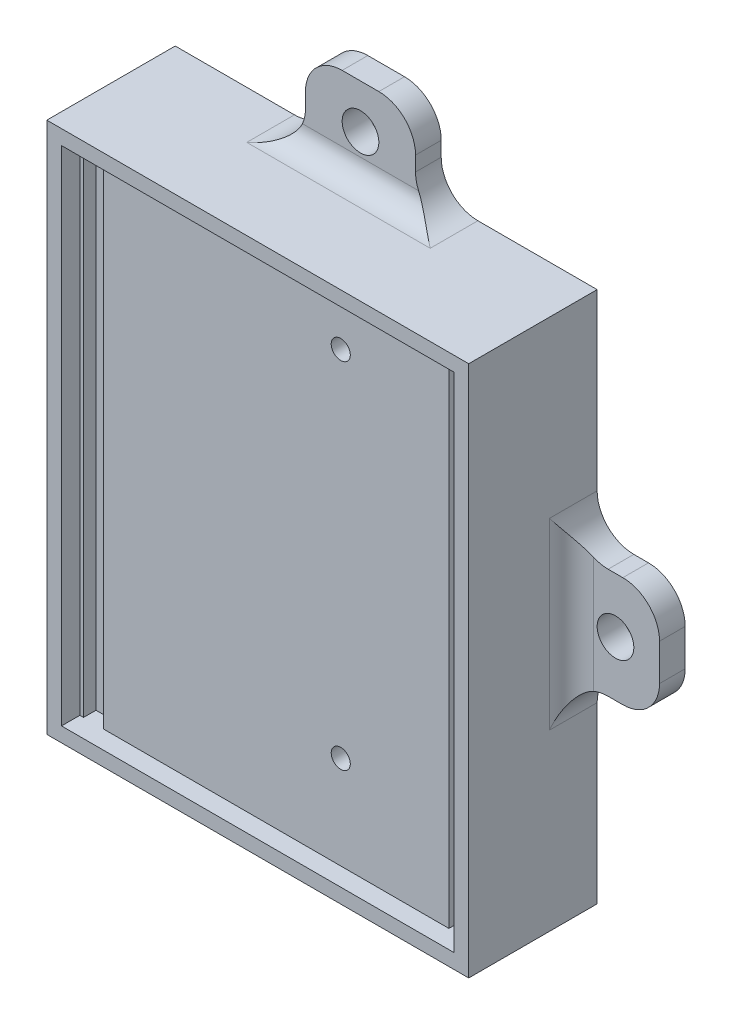
SolidWorks part; units mm, degrees
ref_plane "Front Plane" through (0, 0, 0) normal (0, 0, 1) x (1, 0, 0)
ref_plane "Top Plane" through (0, 0, 0) normal (0, 1, 0) x (1, 0, 0)
ref_plane "Right Plane" through (0, 0, 0) normal (1, 0, 0) x (0, 0, -1)
sketch "Sketch1" plane through (0, 0, 0) normal (0, 0, 1) x (1, 0, 0)
  line L1 (0, 0) -> (53.5, 0)
  line L2 (0, 0) -> (0, 68.5)
  line L3 (0, 68.5) -> (53.5, 68.5)
  line L4 (53.5, 0) -> (53.5, 68.5)
  dimension "D1" = 53.5
  dimension "D2" = 68.5
extrude "Boss-Extrude1" add sketch "Sketch1" along normal blind 15
sketch "Sketch2" plane through (0, 0, 15) normal (0, 0, 1) x (1, 0, 0)
  line L5 (0, 0) -> (53.5, 0)
  line L6 (0, 0) -> (0, 68.5)
  line L7 (0, 68.5) -> (53.5, 68.5)
  line L8 (53.5, 0) -> (53.5, 68.5)
  line L16 (-2, 70.5) -> (-2, -2)
  line L17 (-2, -2) -> (55.5, -2)
  line L18 (55.5, -2) -> (55.5, 70.5)
  line L19 (55.5, 70.5) -> (-2, 70.5)
  line L20 (-2, 70.5) -> (-2, -2)
  line L21 (-2, -2) -> (55.5, -2)
  line L22 (55.5, -2) -> (55.5, 70.5)
  line L23 (55.5, 70.5) -> (-2, 70.5)
  dimension "D1" = 2
extrude "Boss-Extrude2" add sketch "Sketch2" against normal up to surface (15 mm away) and the other way blind 2.5 up to face at (26.75, 34.25, 0)
sketch "Sketch3" plane through (0, 0, 15) normal (0, 0, 1) x (1, 0, 0)
  line L0 (53.5, 68.5) -> (0, 68.5) construction
  line L1 (0.5, 68.5) -> (3.2, 68.5)
  line L2 (0.5, 68.5) -> (0.5, 0)
  line L3 (0.5, 0) -> (3.2, 0)
  line L4 (3.2, 68.5) -> (3.2, 0)
  line L5 (0, 0) -> (53.5, 0) construction
  line L6 (0, 68.5) -> (0, 0) construction
  line L7 (53.5, 68.5) -> (0, 68.5) construction
  line L8 (50.3, 68.5) -> (53, 68.5)
  line L9 (50.3, 68.5) -> (50.3, 0)
  line L10 (50.3, 0) -> (53, 0)
  line L11 (53, 68.5) -> (53, 0)
  line L12 (0, 0) -> (53.5, 0) construction
  line L13 (53.5, 0) -> (53.5, 68.5) construction
  dimension "D1" = 0.5
  dimension "D2" = 2.7
  dimension "D3" = 0.5
  dimension "D4" = 2.7
extrude "Cut-Extrude1" cut sketch "Sketch3" against normal blind 1.7
sketch "Sketch4" plane through (0, 0, 15) normal (0, 0, 1) x (1, 0, 0)
  line L0 (0, 68.5) -> (0, 0) construction
  line L1 (3.2, 0) -> (50.3, 0) construction
  circle A0 centre (35.56, 12.7) radius 1.3
  circle A1 centre (35.56, 60.96) radius 1.3
  dimension "D1" = 35.56
  dimension "D5" = 2.6
  dimension "D6" = 2.6
  dimension "D2" = 35.56
  dimension "D3" = 12.7
  dimension "D4" = 60.96
extrude "Cut-Extrude2" cut sketch "Sketch4" against normal blind 7
sketch "Sketch5" plane through (0, 0, 0) normal (0, 0, -1) x (-1, 0, 0)
  line L0 (2, -2) -> (-55.5, -2) construction
  line L1 (-34.25, -2) -> (-19.25, -2)
  line L2 (-34.25, -2) -> (-34.25, -14)
  line L3 (-34.25, -14) -> (-19.25, -14)
  line L4 (-19.25, -2) -> (-19.25, -14)
  line L5 (2, 70.5) -> (2, -2) construction
  line L6 (2, 26.75) -> (14, 26.75)
  line L7 (2, 26.75) -> (2, 41.75)
  line L8 (2, 41.75) -> (14, 41.75)
  line L9 (14, 26.75) -> (14, 41.75)
  line L10 (-55.5, -2) -> (-55.5, 70.5) construction
  line L11 (-55.5, 26.75) -> (-67.5, 26.75)
  line L12 (-55.5, 26.75) -> (-55.5, 41.75)
  line L13 (-55.5, 41.75) -> (-67.5, 41.75)
  line L14 (-67.5, 26.75) -> (-67.5, 41.75)
  line L15 (-55.5, 70.5) -> (2, 70.5) construction
  line L16 (-34.25, 70.5) -> (-19.25, 70.5)
  line L17 (-34.25, 70.5) -> (-34.25, 82.5)
  line L18 (-34.25, 82.5) -> (-19.25, 82.5)
  line L19 (-19.25, 70.5) -> (-19.25, 82.5)
  circle A0 centre (-61.5, 34.25) radius 2.5
  circle A1 centre (8, 34.25) radius 2.5
  circle A2 centre (-26.75, -8) radius 2.5
  circle A3 centre (-26.75, 76.5) radius 2.5
  point P24 (-55.5, 34.25)
  point P25 (-26.75, -2)
  point P26 (2, 34.25)
  point P27 (-26.75, 70.5)
  point P36 (-26.75, 82.5)
  dimension "D13" = 7.5
  dimension "D15" = 5
  dimension "D16" = 5
  dimension "D17" = 5
  dimension "D18" = 5
  dimension "D21" = 6
  dimension "D22" = 7.5
  dimension "D24" = 6
  dimension "D1" = 15
  dimension "D2" = 15
  dimension "D3" = 15
  dimension "D4" = 15
  dimension "D5" = 12
  dimension "D6" = 12
  dimension "D7" = 12
  dimension "D8" = 12
  dimension "D9" = 7.5
  dimension "D10" = 7.5
  dimension "D11" = 7.5
  dimension "D12" = 7.5
  dimension "D14" = 6
  dimension "D19" = 7.5
  dimension "D20" = 6
  dimension "D23" = 7.5
extrude "Boss-Extrude3" add sketch "Sketch5" against normal blind 3.5
fillet "Fillet1" radius 5 16 edges at (67.5, 41.75, 1.75) (55.5, 41.75, 1.75) (67.5, 26.75, 1.75) (55.5, 26.75, 1.75) (19.25, -2, 1.75) (19.25, -14, 1.75) (34.25, -14, 1.75) (34.25, -2, 1.75) (-14, 26.75, 1.75) (-2, 26.75, 1.75) (-2, 41.75, 1.75) (-14, 41.75, 1.75) (19.25, 70.5, 1.75) (19.25, 82.5, 1.75) (34.25, 70.5, 1.75) (34.25, 82.5, 1.75)
fillet "Fillet2" radius 3 4 edges at (55.5, 34.25, 3.5) (-2, 34.25, 3.5) (26.75, -2, 3.5) (26.75, 70.5, 3.5)
